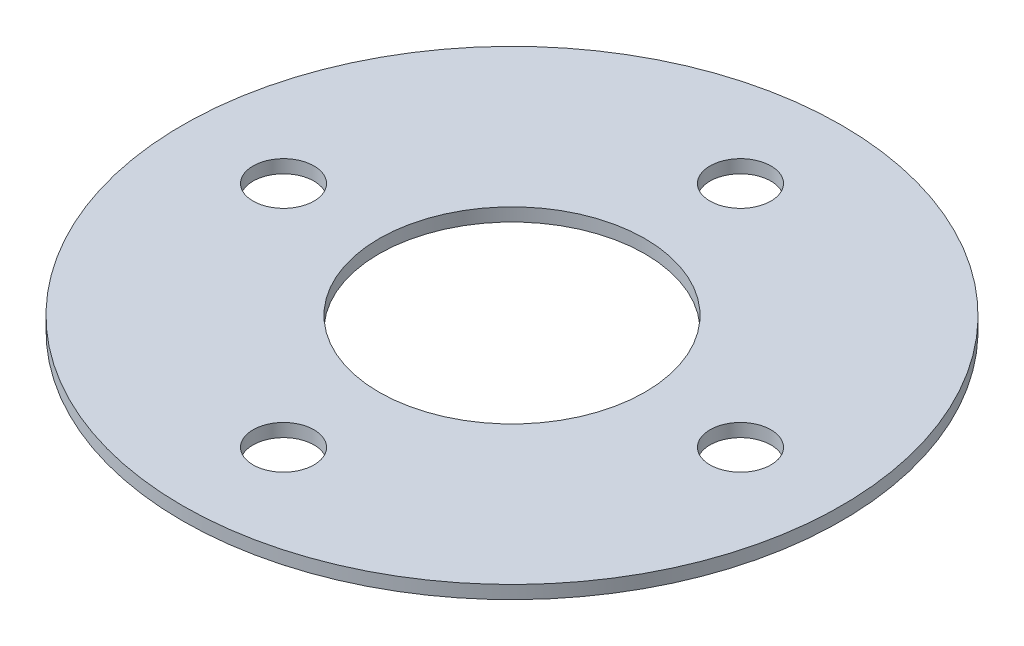
SolidWorks part; units mm, degrees
material "201 Annealed Stainless Steel (SS)"
ref_plane "Front Plane" through (0, 0, 0) normal (0, 0, 1) x (1, 0, 0)
ref_plane "Top Plane" through (0, 0, 0) normal (0, 1, 0) x (1, 0, 0)
ref_plane "Right Plane" through (0, 0, 0) normal (1, 0, 0) x (0, 0, -1)
sketch "Sketch1" plane through (0, 0, 0) normal (0, 1, 0) x (1, 0, 0)
  circle A0 centre (0, 0) radius 21.6364
  circle A1 centre (0, 0) radius 8.7312
  circle A2 centre (0, 15) radius 2
  circle A3 centre (15, 0) radius 2
  circle A4 centre (0, -15) radius 2
  circle A5 centre (-15, 0) radius 2
  point P15 (0, 0)
  dimension "D1" = 43.2728
  dimension "D2" = 17.4625
  dimension "D3" = 4
  dimension "D4" = 15
  dimension "D5" = 4
extrude "Boss-Extrude1" add sketch "Sketch1" along normal blind 0.8636
